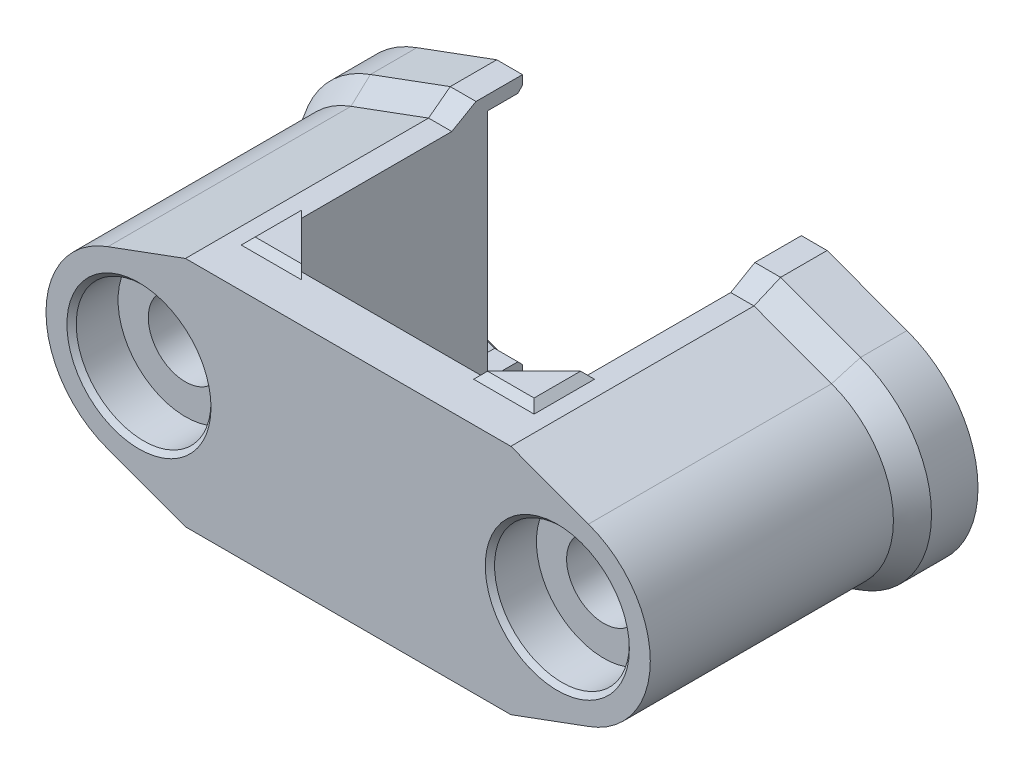
SolidWorks part; units mm, degrees
material "PVC hart"
ref_plane "Ebene vorne" through (0, 0, 0) normal (0, 0, 1) x (1, 0, 0)
ref_plane "Ebene oben" through (0, 0, 0) normal (0, 1, 0) x (1, 0, 0)
ref_plane "Ebene rechts" through (0, 0, 0) normal (1, 0, 0) x (0, 0, -1)
sketch "Skizze2" plane through (0, 0, 0) normal (0, 0, 1) x (1, 0, 0)
  line L0 (0, 0) -> (0, 4.16) construction
  line L1 (9, 0) -> (-9, 0) construction
  line L2 (-6, -2.6458) -> (-6, -5)
  line L7 (6, 5) -> (-6, 5)
  line L8 (6, 5) -> (6, 2.6458)
  line L9 (6, -5) -> (-6, -5)
  line L10 (-6, 5) -> (-6, 2.6458)
  line L11 (6, 5) -> (-6, -5) construction
  line L12 (6, -5) -> (-6, 5) construction
  line L13 (6, -2.6458) -> (6, -5)
  circle A0 centre (-9, 0) radius 1.6
  arc A1 (-6, 2.6458) -> (-6, -2.6458) centre (-9, 0) ccw
  circle A2 centre (9, 0) radius 1.6
  arc A3 (6, 2.6458) -> (6, -2.6458) centre (9, 0) cw
  dimension "D1" = 3.2
  dimension "D2" = 8
  dimension "D3" = 18
  dimension "D4" = 10
  dimension "D5" = 12
extrude "Aufsatz-Linear austragen1" add sketch "Skizze2" along normal blind 12
ref_plane "Ebene1" through (0, 0, 0) normal (0, -1, 0) x (-1, 0, 0)
sketch "Skizze3" plane through (0, 0, 0) normal (0, -1, 0) x (-1, 0, 0)
  line L0 (6, 0) -> (-6, 0) construction
  line L1 (-6, 0) -> (6, 0)
  line L2 (-6, 0) -> (-6, -10)
  line L3 (-6, -10) -> (6, -10)
  line L4 (6, 0) -> (6, -10)
  line L5 (0, -10) -> (0, 0) construction
  dimension "D1" = 10
  dimension "D2" = 12
extrude "Schnitt-Linear austragen1" cut sketch "Skizze3" against normal through all and the other way through all
sketch "Skizze4" plane through (0, 0, 12) normal (0, 0, 1) x (1, 0, 0)
  line L0 (0, 5) -> (0, 0) construction
  line L1 (6, 5) -> (-6, 5) construction
  line L2 (-6, 5) -> (-7, 5)
  line L3 (-7, 5) -> (-10.3385, 3.7694)
  line L4 (-6, 5) -> (-6, 2.6458) construction
  line L5 (-6, 5) -> (-6, 2.6458)
  line L6 (-1.1, 0) -> (1.1, 0) construction
  line L7 (-6, -5) -> (-6, -2.6458)
  line L8 (-7, -5) -> (-10.3385, -3.7694)
  line L9 (-6, -5) -> (-7, -5)
  line L10 (6, -5) -> (7, -5)
  line L11 (7, -5) -> (10.3385, -3.7694)
  line L12 (6, -5) -> (6, -2.6458)
  line L13 (6, 5) -> (6, 2.6458)
  line L14 (7, 5) -> (10.3385, 3.7694)
  line L15 (6, 5) -> (7, 5)
  arc A0 (-6, 2.6458) -> (-6, -2.6458) centre (-9, 0) ccw construction
  arc A1 (-6, 2.6458) -> (-10.3385, 3.7694) centre (-9, 0) ccw
  arc A2 (-6, -2.6458) -> (-10.3385, -3.7694) centre (-9, 0) cw
  arc A3 (6, -2.6458) -> (10.3385, -3.7694) centre (9, 0) ccw
  arc A4 (6, 2.6458) -> (10.3385, 3.7694) centre (9, 0) cw
  arc M5 (-6, 2.6458) -> (-6, -2.6458) centre (-9, 0) ccw
  line M6 (-6, -2.6458) -> (-6, -5)
  line M8 (6, -5) -> (6, -2.6458)
  arc M9 (6, -2.6458) -> (6, 2.6458) centre (9, 0) ccw
  line M10 (6, 2.6458) -> (6, 5)
  line M12 (-6, 5) -> (-6, 2.6458)
  dimension "D1" = 1
extrude "Aufsatz-Linear austragen2" add sketch "Skizze4" against normal through all contours L2 L3 M5 M12 | L9 L8 M6 M5 | L15 L14 M10 M9 | L10 L11 M9 M8 region at (-7.1267, 4.1275, 12) region at (-7.1267, -4.1275, 12) region at (7.1267, -4.1275, 12) region at (7.1267, 4.1275, 12)
sketch "Skizze5" plane through (0, -5, 0) normal (0, -1, 0) x (1, 0, 0)
  line L0 (-6, 10) -> (-4, 10)
  line L1 (6, 10) -> (-6, 10) construction
  line L2 (-4, 10) -> (-6, 8)
  line L3 (-6, 0) -> (-6, 10) construction
  line L4 (-6, 8) -> (-6, 10)
  line L5 (0, 12) -> (0, 10) construction
  line L6 (-7, 12) -> (7, 12) construction
  line L7 (6, 8) -> (6, 10)
  line L8 (4, 10) -> (6, 8)
  line L9 (6, 10) -> (4, 10)
  dimension "D1" = 2
extrude "Aufsatz-Linear austragen3" add sketch "Skizze5" against normal blind 0.2 and the other way blind 0.3
mirror "Spiegeln1" about plane through (0, 0, 0) normal (0, -1, 0) of "Aufsatz-Linear austragen3"
chamfer "Fase3" distance 0.3 angle 45 8 edges at (6, -5, 9) (5, -5, 10) (-6, -5, 9) (-5, -5, 10) (6, 5, 9) (5, 5, 10) (-5, 5, 10) (-6, 5, 9)
ref_plane "Ebene2" through (0, 0, -1.5) normal (0, 0, -1) x (-1, 0, 0)
sketch "Skizze6" plane through (0, 0, -1.5) normal (0, 0, -1) x (-1, 0, 0)
  line L0 (6, -5) -> (7, -5) construction
  line L1 (7, -5) -> (10.3385, -3.7694) construction
  line L2 (7, 5) -> (10.3385, 3.7694) construction
  line L3 (6, 5) -> (7, 5) construction
  line L4 (6, -5) -> (7, -5)
  line L5 (7, -5) -> (10.3385, -3.7694)
  line L6 (7, 5) -> (10.3385, 3.7694)
  line L7 (6, 5) -> (7, 5)
  line L8 (6, 5.6) -> (7.1071, 5.6)
  line L9 (7.1071, 5.6) -> (10.5428, 4.3336)
  line L10 (7.1071, -5.6) -> (10.5428, -4.3336)
  line L11 (6, -5.6) -> (7.1071, -5.6)
  line L12 (6, 5.6) -> (6, 5)
  line L13 (6, -5) -> (6, -5.6)
  line L14 (0, 5) -> (0, -5) construction
  line L15 (-4, 5) -> (4, 5) construction
  line L16 (-4, -5) -> (4, -5) construction
  line L17 (-6, -5) -> (-6, -5.6)
  line L18 (-6, 5.6) -> (-6, 5)
  line L19 (-6, -5.6) -> (-7.1071, -5.6)
  line L20 (-7.1071, -5.6) -> (-10.5428, -4.3336)
  line L21 (-7.1071, 5.6) -> (-10.5428, 4.3336)
  line L22 (-6, 5.6) -> (-7.1071, 5.6)
  line L23 (-6, 5) -> (-7, 5)
  line L24 (-7, 5) -> (-10.3385, 3.7694)
  line L25 (-7, -5) -> (-10.3385, -3.7694)
  line L26 (-6, -5) -> (-7, -5)
  arc A0 (10.3385, -3.7694) -> (10.3385, 3.7694) centre (9, 0) ccw construction
  arc A1 (10.3385, -3.7694) -> (10.3385, 3.7694) centre (9, 0) ccw
  arc A2 (10.5428, -4.3336) -> (10.5428, 4.3336) centre (9, 0) ccw
  arc A3 (-10.5428, -4.3336) -> (-10.5428, 4.3336) centre (-9, 0) cw
  arc A4 (-10.3385, -3.7694) -> (-10.3385, 3.7694) centre (-9, 0) cw
  dimension "D1" = 0.6
extrude "Aufsatz-Linear austragen4" add sketch "Skizze6" against normal blind 2
chamfer "Fase1" distance 0.6 angle 60 9 edges at (-6.5, 5, 0.5) (-8.6692, 4.3847, 0.5) (-13, 0, 0.5) (-6.5, -5, 0.5) (-8.6692, -4.3847, 0.5) (6.5, -5, 0.5) (8.6692, -4.3847, 0.5) (8.6692, 4.3847, 0.5) (6.5, 5, 0.5) first distance on face at (-8.3079, 0, 0.5) first distance on face at (8.3079, 0, 0.5)
sketch "Skizze7" plane through (0, 0, 12) normal (0, 0, 1) x (1, 0, 0)
  circle A0 centre (-9, 0) radius 2.9
  circle A1 centre (9, 0) radius 2.9
  dimension "D1" = 5.8
extrude "Schnitt-Linear austragen2" cut sketch "Skizze7" against normal blind 2
chamfer "Fase2" distance 0.2 angle 45 13 edges at (-6.5, -5, -1.5) (-8.6692, -4.3847, -1.5) (-8.6692, 4.3847, -1.5) (-6.5, 5, -1.5) (6.5, -5, -1.5) (8.6692, -4.3847, -1.5) (13, 0, -1.5) (8.6692, 4.3847, -1.5) (6.5, 5, -1.5) (7.4, 0, 0) (-7.4, 0, 0) (-6.1, 0, 12) (11.9, 0, 12)
